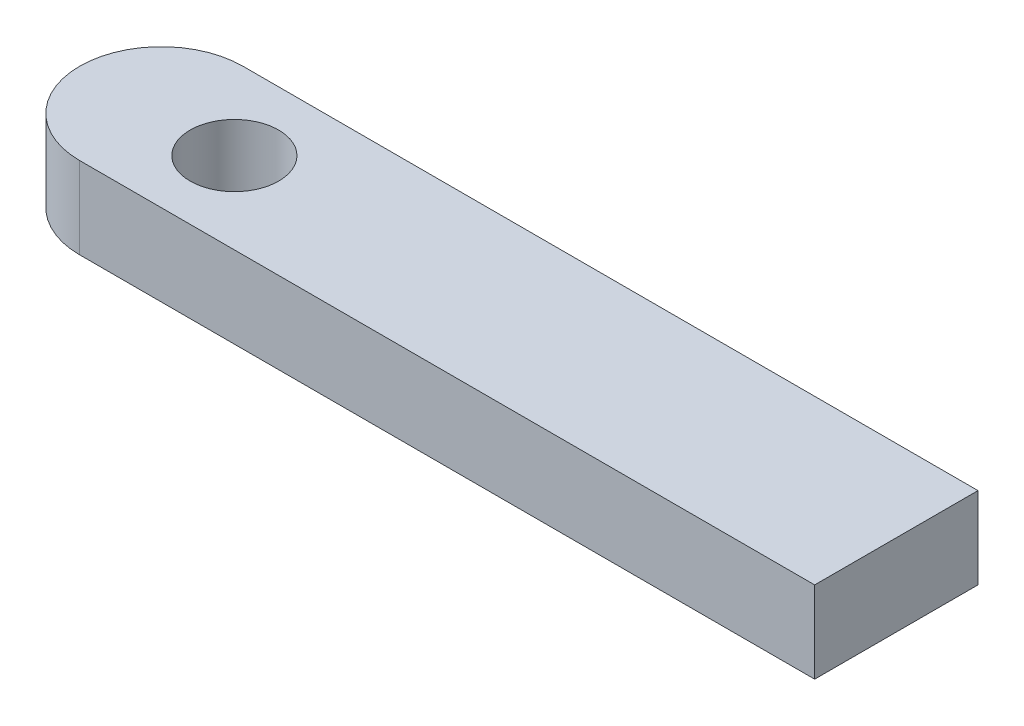
SolidWorks part; units mm, degrees
ref_plane "Front Plane" through (0, 0, 0) normal (0, 0, 1) x (1, 0, 0)
ref_plane "Top Plane" through (0, 0, 0) normal (0, 1, 0) x (1, 0, 0)
ref_plane "Right Plane" through (0, 0, 0) normal (1, 0, 0) x (0, 0, -1)
sketch "Sketch1" plane through (0, 0, 0) normal (0, 1, 0) x (1, 0, 0)
  line L1 (25, -5) -> (-25, -5)
  line L2 (25, -5) -> (25, 5)
  line L3 (25, 5) -> (-25, 5)
  line L4 (-25, -5) -> (-25, 5)
  line L5 (0, 5) -> (0, -5) construction
  line L6 (25, 0) -> (-25, 0) construction
  circle A0 centre (-15.5246, 0) radius 2.7097
  point P0 (0, 0)
  dimension "D1" = 10
  dimension "D2" = 50
extrude "Boss-Extrude2" add sketch "Sketch1" along normal blind 5
fillet "Fillet1" radius 5 2 edges at (-25, 2.5, -5) (-25, 2.5, 5)
